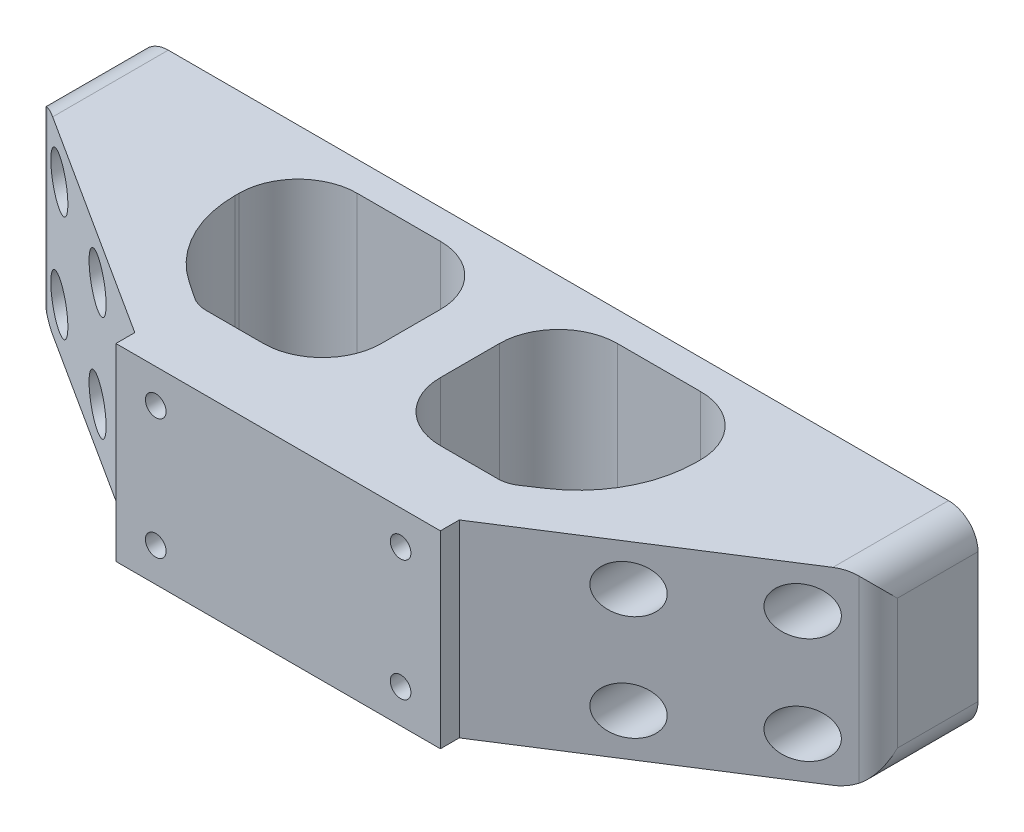
SolidWorks part; units mm, degrees
note: The reader was unsure of these and kept them because the rebuilt part matched: shared geometry of "Sketch13<3>".
material "Nylon 6/10"
ref_plane "Front Plane" through (0, 0, 0) normal (0, 0, 1) x (1, 0, 0)
ref_plane "Top Plane" through (0, 0, 0) normal (0, 1, 0) x (1, 0, 0)
ref_plane "Right Plane" through (0, 0, 0) normal (1, 0, 0) x (0, 0, -1)
sketch "Sketch1" plane through (0, 0, 0) normal (0, 1, 0) x (1, 0, 0)
  line L0 (0, 0) -> (62.625, 0)
  line L1 (75.125, 0) -> (81.125, 0)
  line L2 (62.625, 12.5) -> (62.625, 17.5)
  line L3 (112.5, 0) -> (106.5, 0)
  line L4 (106.5, 0) -> (106.5, 17.5)
  line L5 (106.5, 17.5) -> (62.625, 17.5)
  line L6 (81.125, 0) -> (81.125, 17.5)
  line L7 (81.125, 17.5) -> (62.625, 17.5)
  line L8 (44.125, -17.5) -> (44.125, 17.5)
  line L10 (44.125, 17.5) -> (81.125, 17.5)
  line L11 (81.125, -17.5) -> (81.125, 17.5)
  line L12 (44.125, -17.5) -> (81.125, 17.5) construction
  line L13 (44.125, 17.5) -> (81.125, -17.5) construction
  line L14 (44.125, -17.5) -> (5, -17.5)
  line L15 (5, -17.5) -> (0, -17.5)
  line L16 (0, -17.5) -> (0, -12.5)
  line L17 (0, -12.5) -> (5, -12.5)
  line L18 (5, -12.5) -> (44.125, -12.5)
  line L19 (5, -12.5) -> (5, -17.5)
  line L20 (5, -17.5) -> (5, -55)
  line L21 (0, -55) -> (10, -55)
  line L22 (5, -55) -> (0, -55)
  line L23 (5, -55) -> (5, -17.5)
  line L24 (5, -17.5) -> (0, -17.5)
  line L25 (0, -55) -> (0, -17.5)
  line L26 (10, -55) -> (15, -55)
  line L27 (81.125, -17.5) -> (71.125, -17.5)
  line L28 (71.125, -17.5) -> (15, -55)
  line L29 (15, -55) -> (22.5, -55)
  line L30 (81.125, -17.5) -> (81.125, -22.5)
  line L31 (71.125, -17.5) -> (44.125, -17.5)
  line L32 (22.5, -55) -> (22.5, -60)
  line L33 (22.5, -60) -> (81.125, -22.5)
  line L34 (22.5, -60) -> (0, -60)
  line L35 (0, -60) -> (0, -55)
  line L36 (24.5625, -17.5) -> (48.25, -17.5)
  line L37 (24.5625, -17.5) -> (63.25, -17.5)
  line L38 (38.0567, -39.5946) -> (49.6962, -31.8177)
  line L39 (71.125, -17.5) -> (5, -55)
  line L40 (49.6962, -31.8177) -> (44.125, -17.5)
  line L41 (39.125, -17.5) -> (45.5388, -34.5954)
  line L42 (15, -55) -> (15, -47.5)
  line L43 (15, -47.5) -> (26.225, -47.5)
  line L44 (15, -47.5) -> (5, -47.5)
  line L45 (39.125, -17.5) -> (39.125, -38.8808)
  circle A0 centre (62.625, 0) radius 12.5
  circle A1 centre (44.125, -17.5) radius 5
  circle A2 centre (49.6962, -31.8177) radius 5
  point P9 (62.625, 17.5)
  point P13 (93.8125, 0)
  dimension "D2" = 25
  dimension "D18" = 10
  dimension "D19" = 10
  dimension "D1" = 62.625
  dimension "D3" = 6
  dimension "D4" = 5
  dimension "D6" = 39.125
  dimension "D7" = 5
  dimension "D8" = 5
  dimension "D9" = 5
  dimension "D10" = 37.5
  dimension "D11" = 10
  dimension "D12" = 5
  dimension "D13" = 7.5
  dimension "D14" = 10
  dimension "D15" = 27
  dimension "D16" = 5
  dimension "D17" = 5
  dimension "D20" = 7.5
  dimension "D5" = 2
extrude "Boss-Extrude1" add sketch "Sketch1" along normal blind 32 contours A1 L31 L27 L11 L1 A0 L0 L8 | A2 L38 L28 L29 L32 L33 L30 L27 | L28 A2 | L39 L41 L28 L40 | L40 A2 L41 L39 | A2 L40 A1 L41 | L41 A1 L40 L14 | L37 A1 L8 L31 | L8 A1 L14 | A1 L18 L19 L14 L37 | L19 L17 L16 L15 | L35 L34 L32 L29 L26 L21 | L39 L44 L23 | L42 L44 L39 L21 L26 | L43 L42 L28 | A2 L39 L31 A1 L40 | A2 L28 L39 | L40 A1 L37 L31 | L28 A2 L39 L40 | L39 A2 L40 | A2 L41 A1 L45 L39 | A2 L39 L45 L38 | L39 A2 L41 | L41 A1 | L43 L42 L39
mirror "Mirror1" about plane through (0, 32, 0) normal (-1, 0, 0) of "Boss-Extrude1"
ref_plane "Plane1" through (0, 0, 0) normal (1, 0, 0) x (0, 0, -1)
fillet "Fillet16" radius 10 1 edges at (5, 16, 17.5)
fillet "Fillet18" radius 10 1 edges at (-5, 16, 17.5)
fillet "Fillet22" radius 3 1 edges at (44.125, 16, 12.5)
fillet "Fillet23" radius 3 1 edges at (-44.125, 16, 12.5)
fillet "Fillet30" radius 3 1 edges at (81.125, 16, 22.5)
fillet "Fillet31" radius 3 1 edges at (-81.125, 16, 22.5)
fillet "Fillet34" radius 10 1 edges at (5, 16, 47.5)
fillet "Fillet35" radius 5 1 edges at (-26.225, 16, 47.5)
sketch "Sketch10" plane through (0, 0, 12.5) normal (0, 0, -1) x (-1, 0, 0)
  circle A0 centre (0, 0) radius 169.6109
extrude "Cut-Extrude6" cut sketch "Sketch10" along normal through all
fillet "Fillet37" radius 10 1 edges at (39.125, 16, 17.5)
fillet "Fillet38" radius 20 1 edges at (39.125, 16, 38.8808)
fillet "Fillet39" radius 10 1 edges at (-39.125, 16, 17.5)
fillet "Fillet40" radius 20 1 edges at (-39.125, 16, 38.8808)
sketch "Sketch12" plane through (0, 0, 0) normal (0, -1, 0) x (-1, 0, 0)
  line L0 (-81.125, -12.5) -> (-71.125, -12.5)
  line L1 (81.125, -12.5) -> (-81.125, -12.5) construction
  line L2 (-71.125, -12.5) -> (-71.125, -41.6662)
  line L3 (-71.125, -41.6662) -> (-81.125, -41.6662)
  line L4 (-81.125, -41.6662) -> (-81.125, -12.5)
  dimension "D1" = 10
extrude "Cut-Extrude8" cut sketch "Sketch12" against normal through all
sketch "Sketch9" plane through (0, 0, 60) normal (0, 0, 1) x (1, 0, 0)
  line L0 (0, 0) -> (0, 32)
  line L1 (22.5, 0) -> (-22.5, 0) construction
  line L2 (22.5, 32) -> (-22.5, 32) construction
  line L3 (0, 16) -> (-20.75, 16)
  line L4 (-20.75, 16) -> (-36, 16)
  line L5 (-20.75, 16) -> (-20.75, 5.75)
  line L6 (-20.75, 16) -> (-20.75, 26.25)
  circle A1 centre (-36, 16) radius 1.5
  circle A2 centre (-20.75, 5.75) radius 1.75
  circle A4 centre (-20.75, 26.25) radius 1.75
  dimension "D2" = 10.25
  dimension "D4" = 3
  dimension "D5" = 3.5
  dimension "D7" = 3.5
  dimension "D1" = 20.75
  dimension "D3" = 15.25
  dimension "D6" = 10.25
extrude "Cut-Extrude9" cut sketch "Sketch9" against normal up to surface (12.5 mm away) up to face at (-14.8542, 16, 47.5)
fillet "Fillet41" radius 10 1 edges at (-5, 16, 47.5)
fillet "Fillet42" radius 5 1 edges at (26.225, 16, 47.5)
mirror "Mirror5" about plane through (0, 0, 0) normal (1, 0, 0) of "Cut-Extrude9"
sketch "Sketch13" plane through (0, 0, 60) normal (0, 0, 1) x (1, 0, 0)
  line L0 (0, 0) -> (0, 32)
  line L1 (22.5, 0) -> (-22.5, 0) construction
  line L2 (22.5, 32) -> (-22.5, 32) construction
  line L3 (0, 16) -> (63, 16)
  line L8 (63, 16) -> (63, 7)
  line L9 (63, 16) -> (63, 25)
  line L10 (63, 25) -> (45, 25)
  line L11 (45, 25) -> (45, 7.15)
  circle A0 centre (45, 7.15) radius 2.375
  circle A1 centre (45, 7.15) radius 4
  circle A2 centre (45, 25) radius 4
  circle A3 centre (45, 25) radius 2.375
  circle A4 centre (63, 25) radius 2.375
  circle A5 centre (63, 25) radius 4
  circle A6 centre (63, 7) radius 2.375
  circle A7 centre (63, 7) radius 4
  dimension "D5" = 4.75
  dimension "D6" = 8
  dimension "D7" = 8
  dimension "D8" = 4.75
  dimension "D9" = 8
  dimension "D10" = 8
  dimension "D11" = 4.75
  dimension "D12" = 4.75
  dimension "D1" = 63
  dimension "D2" = 9
  dimension "D3" = 9
  dimension "D4" = 18
extrude "Cut-Extrude10" cut sketch "Sketch13" against normal through all and the other way through all contours A6 | A0 | A3 | A4
extrude "Cut-Extrude11" cut sketch "Sketch13<3>" against normal blind 35
sketch "Sketch13<3>" plane through (0, 0, 60) normal (0, 0, 1) x (1, 0, 0) same geometry as "Sketch13"
mirror "Mirror6" about plane through (0, 0, 0) normal (1, 0, 0) of "Cut-Extrude11", "Cut-Extrude10"
fillet "Fillet44" radius 5 3 edges at (71.125, 16, 28.8966) (71.125, 32, 20.6983) (71.125, 0, 20.6983)
mirror "Mirror7" about plane through (0, 0, 0) normal (1, 0, 0) of "Cut-Extrude8"
fillet "Fillet45" radius 5 3 edges at (-71.125, 16, 28.8966) (-71.125, 32, 20.6983) (-71.125, 0, 20.6983)
sketch "Sketch14" plane through (0, 0, 0) normal (0, -1, 0) x (1, 0, 0)
  line L0 (-22.5, 60) -> (-27.5, 60)
  line L1 (-27.5, 60) -> (-27.5, 56.8017)
  line L2 (-22.5, 60) -> (-66.125, 32.0949) construction
  line L3 (-27.5, 56.8017) -> (-22.5, 60)
  line M24 (-22.5, 60) -> (-66.125, 32.0949)
  dimension "D1" = 5
extrude "Boss-Extrude2" add sketch "Sketch14" against normal up to surface (32 mm away) contours L0 L1 M24 up to face at (-22.988, 32, 34.1416)
mirror "Mirror8" about plane through (0, 0, 0) normal (1, 0, 0) of "Boss-Extrude2"
